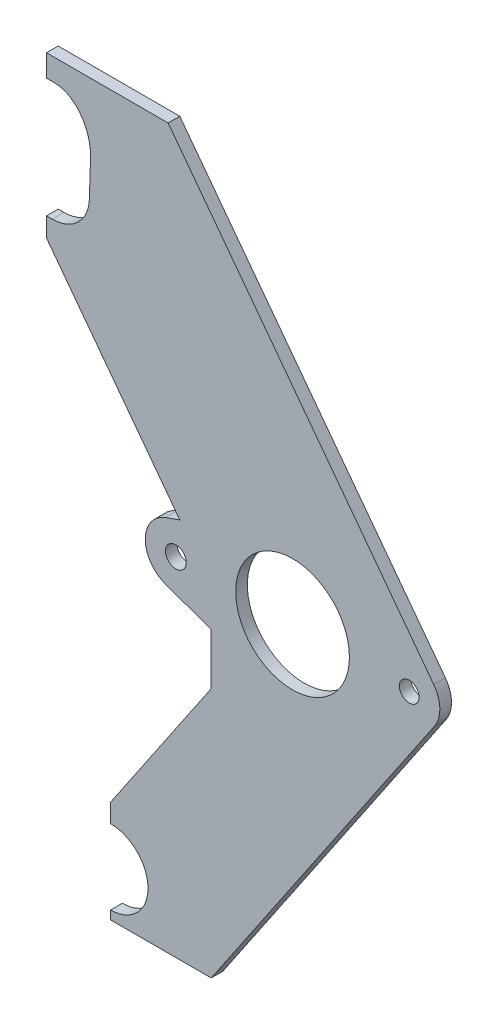
SolidWorks part; units mm, degrees
ref_plane "Front Plane" through (0, 0, 0) normal (0, 0, 1) x (1, 0, 0)
ref_plane "Top Plane" through (0, 0, 0) normal (0, 1, 0) x (1, 0, 0)
ref_plane "Right Plane" through (0, 0, 0) normal (1, 0, 0) x (0, 0, -1)
sketch "Sketch1" plane through (0, 0, 0) normal (0, 0, 1) x (1, 0, 0)
  line L4 (-42.5313, -7.0599) -> (-7.0875, -19.7678)
  line L6 (7.0875, -19.7678) -> (42.5312, -7.0599)
  line L10 (42.5313, 7.0599) -> (7.0875, 19.7678)
  line L12 (-43.5438, -9.8839) -> (-8.1, -22.5918)
  line L13 (8.1, -22.5918) -> (43.5437, -9.8839)
  line L14 (43.5437, 9.8839) -> (8.1, 22.5918)
  line L15 (-8.1, 22.5918) -> (-43.5438, 9.8839)
  line L16 (0, 0) -> (0, -103.21) construction
  line L17 (0, -103.21) -> (-62.35, -103.21) construction
  line L18 (-62.35, -83.9706) -> (-62.35, -90.41)
  line L19 (-62.35, -116.01) -> (-62.35, -118.9706)
  line L20 (-62.35, -118.9706) -> (-27.8815, -118.9706)
  line L21 (-27.8815, -118.9706) -> (48.6942, -5.8874)
  line L22 (-62.35, -83.9706) -> (-27.8815, -33.0692)
  line L23 (-27.8815, -33.0692) -> (-27.8815, -15.4994)
  line L24 (-40, 0) -> (40, 0) construction
  line L25 (0, 0) -> (0, 100) construction
  line L26 (0, 100) -> (-84.35, 100) construction
  line L27 (-84.35, 127.5) -> (-84.35, 72.5)
  line L28 (-84.35, 72.5) -> (-37.5566, 10.2117)
  line L29 (-84.35, 127.5) -> (-42.6503, 127.5)
  line L30 (-42.6503, 127.5) -> (48.395, 6.3067)
  line L32 (-7.0875, 19.7678) -> (-42.5312, 7.0599) construction
  circle A15 centre (-40, 0) radius 3.5658
  circle A16 centre (40, 0) radius 3.3865
  circle A17 centre (0, 0) radius 19.5
  arc A18 (-42.5312, 7.0599) -> (-42.5313, -7.0599) centre (-40, 0) ccw
  arc A19 (-7.0875, -19.7678) -> (7.0875, -19.7678) centre (0, 0) ccw
  arc A20 (42.5312, -7.0599) -> (42.5313, 7.0599) centre (40, 0) ccw
  arc A21 (7.0875, 19.7678) -> (-7.0875, 19.7678) centre (0, 0) ccw
  arc A22 (-8.1, -22.5918) -> (8.1, -22.5918) centre (0, 0) ccw
  arc A23 (43.5437, -9.8839) -> (43.5437, 9.8839) centre (40, 0) ccw
  arc A24 (8.1, 22.5918) -> (-8.1, 22.5918) centre (0, 0) ccw
  arc A25 (-43.5438, 9.8839) -> (-43.5438, -9.8839) centre (-40, 0) ccw
  circle A26 centre (-62.35, -103.21) radius 12.8
  point P36 (-62.35, -103.21)
  point P49 (-84.35, 100)
  dimension "D1" = 39
  dimension "D3" = 3
  dimension "D4" = 103.21
  dimension "D5" = 62.35
  dimension "D6" = 25.6
  dimension "D9" = 22
  dimension "D10" = 55
  dimension "D12" = 40
  dimension "D2" = 80
  dimension "D7" = 35
  dimension "D8" = 100
  dimension "D11" = 40
extrude "Boss-Extrude1" add sketch "Sketch1" along normal blind 4 contours A25 L15 A24 L14 A23 L30 L29 L27 L28 | L15 A25 L12 A22 L13 A23 L14 A24 A15 A16 A17 | A26 L19 L20 L21 A23 L13 A22 L12 L23 L22 L18 region at (-49.3817, 0, 0) region at (-16.9741, -63.3689, 0) region at (-35.0338, 67.3914, 0)
sketch "Sketch2" plane through (0, 0, 0) normal (0, 0, -1) x (-1, 0, 0)
  line L0 (82.35, 79.0815) -> (84.35, 79.0815)
  line L1 (84.35, 127.5) -> (84.35, 72.5) construction
  line L2 (69.6567, 91.368) -> (69.2547, 103.708)
  line L3 (81.7645, 119.9441) -> (84.35, 119.9441)
  line L4 (84.35, 119.9441) -> (84.35, 79.0815)
  arc A0 (82.35, 104.4815) -> (82.35, 79.0815) centre (82.35, 91.7815) ccw
  arc A1 (69.6567, 91.368) -> (82.35, 79.0815) centre (82.35, 91.7815) ccw
  spline S0 degree 3 poles (70.7283, 96.9027) (65.7505, 108.665) (71.1529, 119.9441) (81.7645, 119.9441) knots 0 0 0 0 1 1 1 1 weights 1 0.680947 0.680947 1
  spline S1 degree 3 poles (69.2547, 103.708) (68.9344, 113.5381) (74.4715, 119.9441) (81.7645, 119.9441) knots 0.236559 0.236559 0.236559 0.236559 1 1 1 1 weights 0.827139 0.698802 0.756422 1
extrude "Cut-Extrude1" cut sketch "Sketch2" against normal up to surface (4 mm away) up to face at (-37.682, -15.8192, 4)
